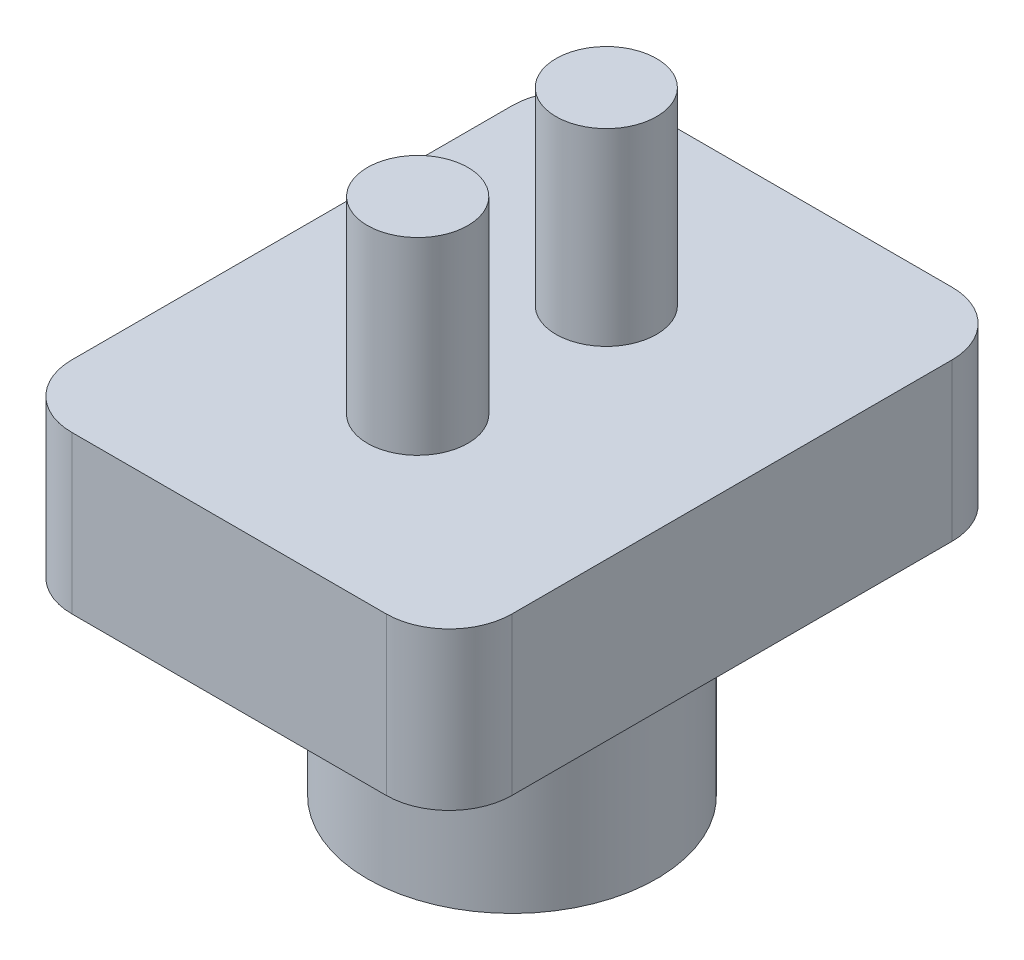
SolidWorks part; units mm, degrees
ref_plane "Alzado" through (0, 0, 0) normal (0, 0, 1) x (1, 0, 0)
ref_plane "Planta" through (0, 0, 0) normal (0, 1, 0) x (1, 0, 0)
ref_plane "Vista lateral" through (0, 0, 0) normal (1, 0, 0) x (0, 0, -1)
sketch "Sketch1" plane through (0, 0, 0) normal (0, 1, 0) x (1, 0, 0)
  line L1 (-7, -9) -> (7, -9)
  line L2 (-7, -9) -> (-7, 9)
  line L3 (-7, 9) -> (7, 9)
  line L4 (7, -9) -> (7, 9)
  line L5 (-7, -9) -> (7, 9) construction
  line L6 (-7, 9) -> (7, -9) construction
  circle A0 centre (0, 0) radius 2.8
  circle A1 centre (0, 0) radius 4.6
  point P7 (0, 0)
  dimension "D1" = 5.6
  dimension "D2" = 9.2
  dimension "D3" = 18
  dimension "D4" = 14
extrude "Boss-Extrude1" add sketch "Sketch1" along normal blind 7 contours A1 A0 region at (-4.4699, 0, 0)
extrude "Boss-Extrude2" add sketch "Sketch1<3>" along normal blind 5 from offset 7 contours L1 L4 L3 L2 A1 | A1 A0 | A0 region at (-6.772, 0, 0) region at (0, 0, 0) region at (-4.4699, 0, 0)
sketch "Sketch1<3>" plane through (0, 0, 0) normal (0, 1, 0) x (1, 0, 0) same geometry as "Sketch1"
sketch "Sketch2" plane through (0, 12, 0) normal (0, 1, 0) x (1, 0, 0)
  line L0 (0, -3) -> (0, 3) construction
  circle A0 centre (0, 3) radius 1.6
  circle A1 centre (0, -3) radius 1.6
  point P4 (0, 0)
  dimension "D1" = 3.2
  dimension "D2" = 3.2
  dimension "D3" = 3
extrude "Boss-Extrude3" add sketch "Sketch2" along normal blind 6
fillet "Fillet1" radius 2 4 edges at (7, 9.5, 9) (-7, 9.5, 9) (-7, 9.5, -9) (7, 9.5, -9)
